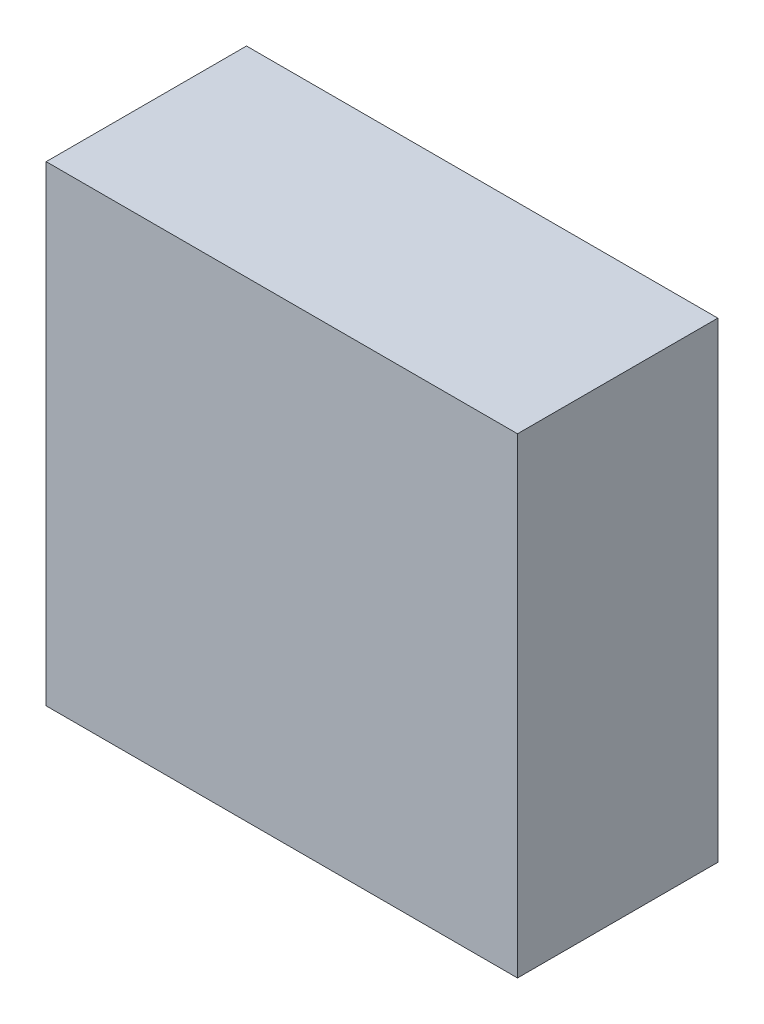
SolidWorks part; units mm, degrees
material "Custom Plastic"
ref_plane "Front Plane" through (0, 0, 0) normal (0, 0, 1) x (1, 0, 0)
ref_plane "Top Plane" through (0, 0, 0) normal (0, 1, 0) x (1, 0, 0)
ref_plane "Right Plane" through (0, 0, 0) normal (1, 0, 0) x (0, 0, -1)
other "Configuration Table"
sketch "Sketch1" plane through (0, 0, 0) normal (0, 0, 1) x (1, 0, 0)
  circle A0 centre (0, 0) radius 150
  dimension "D1" = 300
extrude "Boss-Extrude1" add sketch "Sketch1" along normal mid plane 100
sketch "Sketch2" plane through (0, 0, 0) normal (0, 0, 1) x (1, 0, 0)
  line L1 (-200, -200) -> (200, -200)
  line L2 (-200, -200) -> (-200, 200)
  line L3 (-200, 200) -> (200, 200)
  line L4 (200, -200) -> (200, 200)
  line L5 (-200, -200) -> (200, 200) construction
  line L6 (-200, 200) -> (200, -200) construction
  circle A0 centre (0, 0) radius 175
  dimension "D1" = 350
  dimension "D2" = 400
extrude "Boss-Extrude2" add sketch "Sketch2" along normal mid plane 120 separate body
sketch "Sketch3" plane through (0, 0, 60) normal (0, 0, 1) x (1, 0, 0)
  line L4 (200, -200) -> (200, 200)
  line L5 (200, 200) -> (-200, 200)
  line L6 (-200, 200) -> (-200, -200)
  line L7 (-200, -200) -> (200, -200)
  line L8 (200, -200) -> (200, 200)
  line L9 (200, 200) -> (-200, 200)
  line L10 (-200, 200) -> (-200, -200)
  line L11 (-200, -200) -> (200, -200)
  dimension "D1" = 0
extrude "Boss-Extrude3" add sketch "Sketch3" along normal blind 25
mirror "Mirror1" about plane through (0, 0, 0) normal (0, 0, 1) of "Boss-Extrude3"
